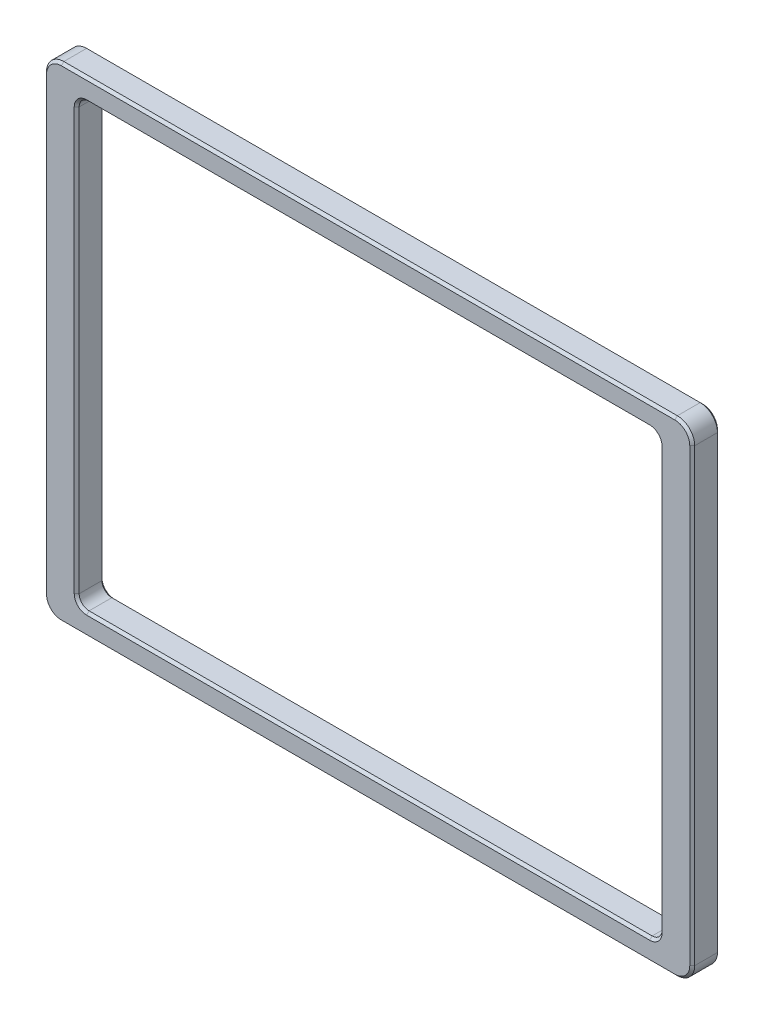
SolidWorks part; units mm, degrees
ref_plane "Front" through (0, 0, 0) normal (0, 0, 1) x (1, 0, 0)
ref_plane "Top" through (0, 0, 0) normal (0, 1, 0) x (1, 0, 0)
ref_plane "Right" through (0, 0, 0) normal (1, 0, 0) x (0, 0, -1)
sketch "Sketch1" plane through (0, 0, 0) normal (0, 0, 1) x (1, 0, 0)
  line L12 (-65.5, 45.5) -> (-65.5, -45.5)
  line L13 (-62, -49) -> (62, -49)
  line L14 (65.5, -45.5) -> (65.5, 45.5)
  line L15 (62, 49) -> (-62, 49)
  line L16 (-65.5, 45.5) -> (-65.5, -45.5)
  line L17 (-62, -49) -> (62, -49)
  line L18 (65.5, -45.5) -> (65.5, 45.5)
  line L19 (62, 49) -> (-62, 49)
  line L25 (-56.9, 44.6) -> (56.9, 44.6)
  line L26 (-58.9, 42.6) -> (-58.9, -42.6)
  line L27 (-56.9, -44.6) -> (56.9, -44.6)
  line L28 (58.9, 42.6) -> (58.9, -42.6)
  line L29 (-58.9, 44.6) -> (58.9, -44.6) construction
  line L30 (-58.9, -44.6) -> (58.9, 44.6) construction
  arc A8 (-62, 49) -> (-65.5, 45.5) centre (-62, 45.5) ccw
  arc A9 (-65.5, -45.5) -> (-62, -49) centre (-62, -45.5) ccw
  arc A10 (62, -49) -> (65.5, -45.5) centre (62, -45.5) ccw
  arc A11 (65.5, 45.5) -> (62, 49) centre (62, 45.5) ccw
  arc A12 (-62, 49) -> (-65.5, 45.5) centre (-62, 45.5) ccw
  arc A13 (-65.5, -45.5) -> (-62, -49) centre (-62, -45.5) ccw
  arc A14 (62, -49) -> (65.5, -45.5) centre (62, -45.5) ccw
  arc A15 (65.5, 45.5) -> (62, 49) centre (62, 45.5) ccw
  arc A21 (56.9, -44.6) -> (58.9, -42.6) centre (56.9, -42.6) ccw
  arc A22 (56.9, 44.6) -> (58.9, 42.6) centre (56.9, 42.6) cw
  arc A23 (-56.9, 44.6) -> (-58.9, 42.6) centre (-56.9, 42.6) ccw
  arc A24 (-58.9, -42.6) -> (-56.9, -44.6) centre (-56.9, -42.6) ccw
  point P0 (0, 0)
  dimension "D4" = 2
  dimension "D2" = 6.6
  dimension "D3" = 4.4
  dimension "D1" = 0.5
extrude "Boss-Extrude1" add sketch "Sketch1" along normal up to surface (5.6 mm away)
chamfer "Deburs" distance 0.5 angle 45 32 edges at (-64.4749, 47.9749, 5.6) (0, 49, 5.6) (64.4749, 47.9749, 5.6) (65.5, 0, 5.6) (64.4749, -47.9749, 5.6) (0, -49, 5.6) (-64.4749, -47.9749, 5.6) (-65.5, 0, 5.6) (58.9, 0, 5.6) (58.3142, 44.0142, 5.6) (0, 44.6, 5.6) (-58.3142, 44.0142, 5.6) (-58.9, 0, 5.6) (-58.3142, -44.0142, 5.6) (0, -44.6, 5.6) (58.3142, -44.0142, 5.6) (0, -44.6, 0) (-58.3142, -44.0142, 0) (-58.9, 0, 0) (-58.3142, 44.0142, 0) (0, 44.6, 0) (58.3142, 44.0142, 0) (58.9, 0, 0) (58.3142, -44.0142, 0) (-65.5, 0, 0) (-64.4749, -47.9749, 0) (0, -49, 0) (64.4749, -47.9749, 0) (65.5, 0, 0) (64.4749, 47.9749, 0) (0, 49, 0) (-64.4749, 47.9749, 0)
